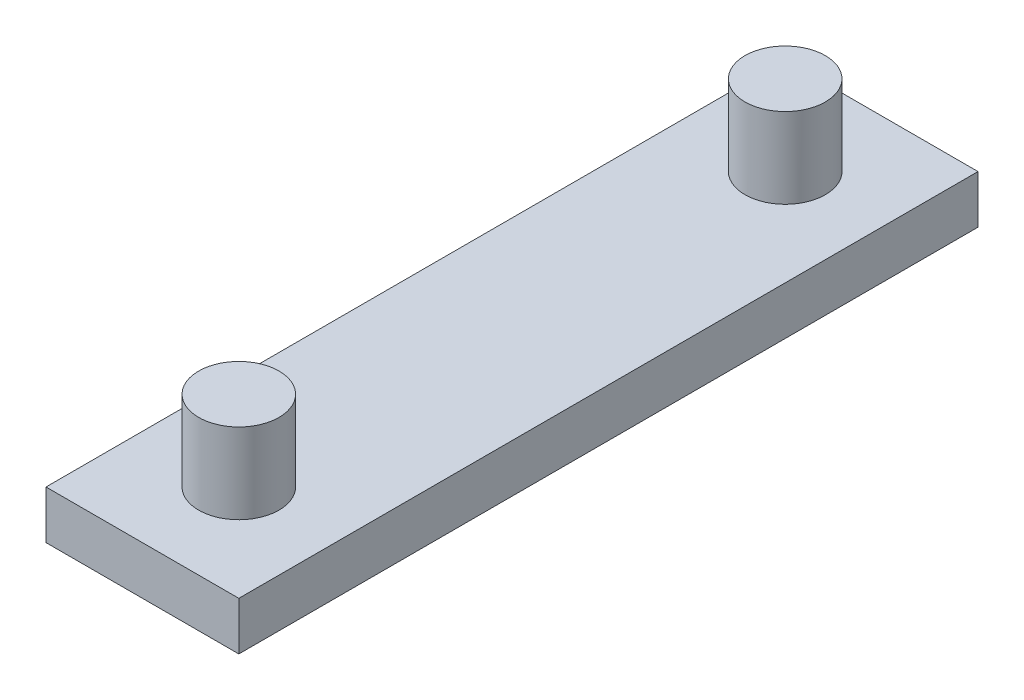
SolidWorks part; units mm, degrees
ref_plane "Front Plane" through (0, 0, 0) normal (0, 0, 1) x (1, 0, 0)
ref_plane "Top Plane" through (0, 0, 0) normal (0, 1, 0) x (1, 0, 0)
ref_plane "Right Plane" through (0, 0, 0) normal (1, 0, 0) x (0, 0, -1)
sketch "Sketch2" plane through (0, 0, 0) normal (0, 1, 0) x (1, 0, 0)
  line L1 (-6.1699, -22.8567) -> (5.8301, -22.8567)
  line L2 (-6.1699, -22.8567) -> (-6.1699, 23.1433)
  line L3 (-6.1699, 23.1433) -> (5.8301, 23.1433)
  line L4 (5.8301, -22.8567) -> (5.8301, 23.1433)
  dimension "D1" = 46
  dimension "D2" = 12
sketch "Sketch3" plane through (0, 0, 0) normal (0, 1, 0) x (1, 0, 0)
  line L2 (5.8301, -22.8567) -> (5.8301, 23.1433) construction
  line L4 (-6.1699, 23.1433) -> (5.8301, 23.1433) construction
  line L5 (5.8301, 0.1433) -> (-6.1699, 0.1433) construction
  line L6 (-6.1699, -22.8567) -> (-6.1699, 23.1433) construction
  circle A2 centre (-0.1699, 17.1433) radius 2.5
  circle A3 centre (-0.1699, -16.8567) radius 2.5
  dimension "D3" = 5
  dimension "D1" = 6
  dimension "D2" = 6
  dimension "D4" = 23
extrude "Boss-Extrude4" add sketch "Sketch3" along normal blind 8
extrude "Boss-Extrude5" add sketch "Sketch2" along normal blind 3
